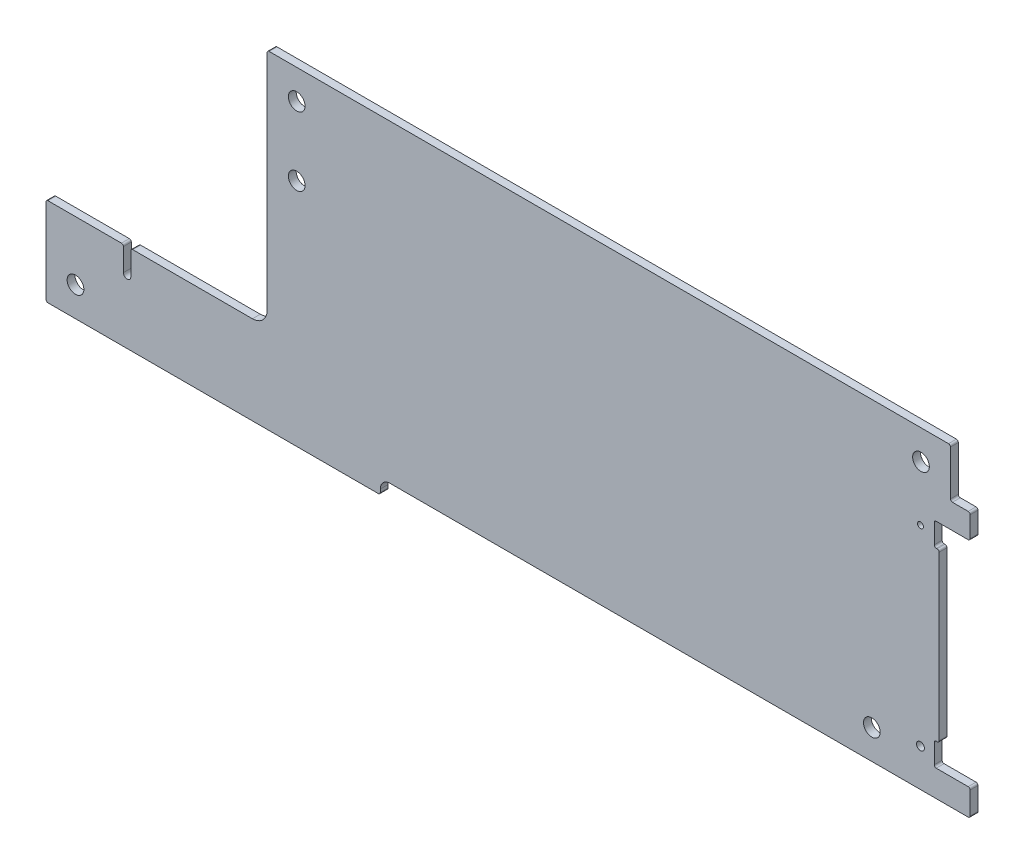
SolidWorks part; units mm, degrees
ref_plane "Front Plane" through (0, 0, 0) normal (0, 0, 1) x (1, 0, 0)
ref_plane "Top Plane" through (0, 0, 0) normal (0, 1, 0) x (1, 0, 0)
ref_plane "Right Plane" through (0, 0, 0) normal (1, 0, 0) x (0, 0, -1)
sketch "Sketch2" plane through (0, 0, 0) normal (0, 0, 1) x (1, 0, 0)
  line L0 (68, -2) -> (68, -3)
  line L1 (70, 0) -> (188, 0)
  line L2 (0, 0) -> (0, 15)
  line L3 (45, 63.8) -> (188, 63.8)
  line L4 (188, 0) -> (188, 63.8)
  line L11 (0, 15) -> (42, 15)
  line L12 (45, 63.8) -> (45, 18)
  line L13 (68, -3) -> (0, -3)
  line L14 (0, -3) -> (0, 0)
  arc A0 (42, 15) -> (45, 18) centre (42, 18) ccw
  arc A2 (68, -2) -> (70, 0) centre (70, -2) cw
  dimension "D7" = 3
  dimension "D8" = 2
  dimension "D1" = 63.8
  dimension "D2" = 188
  dimension "D3" = 15
  dimension "D4" = 45
  dimension "D5" = 3
  dimension "D6" = 120
extrude "Boss-Extrude1" add sketch "Sketch2" along normal blind 1.6
sketch "Sketch4" plane through (0, 0, 0) normal (0, 0, -1) x (-1, 0, 0)
  line L0 (-188, 49.271) -> (-188, 48.871)
  line L1 (-181.1, 48.871) -> (-187.6, 48.871)
  line L2 (-189.75, 27.121) -> (-173.65, 27.121) construction
  line L14 (-70, 0) -> (-188, 0) construction
  line L15 (-181.7, 43.721) -> (-181.7, 10.521)
  line L16 (-181.3, 10.121) -> (-181.1, 10.121)
  line L17 (-180.7, 9.721) -> (-180.7, 5.771)
  line L18 (-181.1, 5.371) -> (-187.6, 5.371)
  line L19 (-188, 0) -> (-188, 63.8) construction
  line L20 (-188, 5.371) -> (-188, 48.871)
  line L21 (-188, 4.971) -> (-188, 5.371)
  line L22 (-180.7, 44.521) -> (-180.7, 48.471)
  line L23 (-181.3, 44.121) -> (-181.1, 44.121)
  arc A9 (-180.7, 5.771) -> (-181.1, 5.371) centre (-181.1, 5.771) cw
  arc A10 (-181.7, 10.521) -> (-181.3, 10.121) centre (-181.3, 10.521) ccw
  arc A11 (-181.1, 10.121) -> (-180.7, 9.721) centre (-181.1, 9.721) cw
  arc A12 (-187.6, 5.371) -> (-188, 4.971) centre (-187.6, 4.971) ccw
  arc A13 (-187.6, 48.871) -> (-188, 49.271) centre (-187.6, 49.271) cw
  arc A14 (-181.1, 44.121) -> (-180.7, 44.521) centre (-181.1, 44.521) ccw
  arc A15 (-181.7, 43.721) -> (-181.3, 44.121) centre (-181.3, 43.721) cw
  arc A16 (-180.7, 48.471) -> (-181.1, 48.871) centre (-181.1, 48.471) ccw
  circle A17 centre (-177.9, 46.591) radius 0.6
  circle A18 centre (-177.9, 7.651) radius 0.8
  point P2 (-181.7, 44.121)
  point P11 (-181.7, 27.121)
  point P16 (-181.7, 10.121)
  point P23 (-182.15, 27.121)
  point P31 (-188, 27.121)
  point P37 (-188, 27.121)
  dimension "D1" = 27.121
  dimension "D12" = 19.47
  dimension "D13" = 19.47
  dimension "D6" = 0.4
  dimension "D7" = 0.4
  dimension "D10" = 1.6
  dimension "D11" = 1.2
  dimension "D2" = 17
  dimension "D3" = 6.3
  dimension "D4" = 43.5
  dimension "D5" = 7.3
  dimension "D8" = 10.1
  dimension "D9" = 10.1
extrude "Cut-Extrude1" cut sketch "Sketch4" against normal through all
sketch "Sketch5" plane through (0, 0, 1.6) normal (0, 0, 1) x (1, 0, 0)
  line L0 (42, 15) -> (0, 15) construction
  line L1 (15.75, 15) -> (17.25, 15)
  line L2 (15.75, 15) -> (15.75, 10)
  line L4 (17.25, 15) -> (17.25, 10)
  line L5 (0, 15) -> (0, -3) construction
  arc A0 (15.75, 10) -> (17.25, 10) centre (16.5, 10) ccw
  point P7 (16.5, 9.25)
  dimension "D1" = 1.5
  dimension "D2" = 5.75
  dimension "D3" = 16.5
extrude "Cut-Extrude2" cut sketch "Sketch5" against normal through all
sketch "Sketch6" plane through (0, 0, 1.6) normal (0, 0, 1) x (1, 0, 0)
  line L1 (188, 63.8) -> (184, 63.8)
  line L2 (188, 63.8) -> (188, 53.871)
  line L3 (187.6, 53.871) -> (184.4, 53.871)
  line L4 (184, 63.8) -> (184, 54.271)
  line L6 (181.1, 48.871) -> (187.6, 48.871) construction
  line L8 (188, 53.871) -> (188, 53.471)
  arc A0 (184.4, 53.871) -> (184, 54.271) centre (184.4, 54.271) cw
  arc A1 (187.6, 53.871) -> (188, 53.471) centre (187.6, 53.471) cw
  dimension "D3" = 0.4
  dimension "D4" = 0.4
  dimension "D1" = 5
  dimension "D2" = 4
extrude "Cut-Extrude3" cut sketch "Sketch6" against normal through all
fillet "Fillet1" radius 0.4 8 edges at (15.75, 15, 0.8) (17.25, 15, 0.8) (0, -3, 0.8) (68, -3, 0.8) (0, 15, 0.8) (45, 63.8, 0.8) (188, 0, 0.8) (184, 63.8, 0.8)
hole_wizard "M3 Clearance Hole1" positions "Sketch7" profile "Sketch8" hole size "M3" standard "ANSI Metric" end condition through all
sketch "Sketch7" plane through (0, 0, 0) normal (0, 0, -1) x (-1, 0, 0)
  line L0 (-188, 49.271) -> (-188, 53.471) construction
  line L1 (-183.6, 63.8) -> (-45.4, 63.8) construction
  line L2 (-45, 63.4) -> (-45, 18) construction
  line L3 (-70, 0) -> (-187.6, 0) construction
  line L4 (-188, 0.4) -> (-188, 4.971) construction
  line L5 (-0.4, -3) -> (-67.6, -3) construction
  line L6 (0, 14.6) -> (0, -2.6) construction
  point P0 (-178, 57.8)
  point P2 (-51, 57.8)
  point P4 (-6, 3)
  point P6 (-168, 6)
  point P23 (-51, 43.8)
  dimension "D1" = 10
  dimension "D2" = 6
  dimension "D3" = 6
  dimension "D4" = 6
  dimension "D5" = 6
  dimension "D6" = 20
  dimension "D7" = 6
  dimension "D8" = 6
  dimension "D9" = 20
  dimension "D10" = 6
sketch "Sketch8" plane through (178, 57.8, 0) normal (1, 0, 0) x (0, 1, 0)
  line L0 (0, 0) -> (0, 1.6)
  line L1 (0, 1.6) -> (1.7, 1.6)
  line L2 (1.7, 1.6) -> (1.7, 0)
  line L5 (1.7, 0) -> (0, 0)
  line L11 (0, -6.35) -> (0, 107.95) construction
  dimension "Thru Hole Dia." = 3.4
  dimension "Thru Hole Depth" = 1.6
ref_plane "Plane1" through (0, 0, 0.8) normal (0, 0, -1) x (-1, 0, 0)
